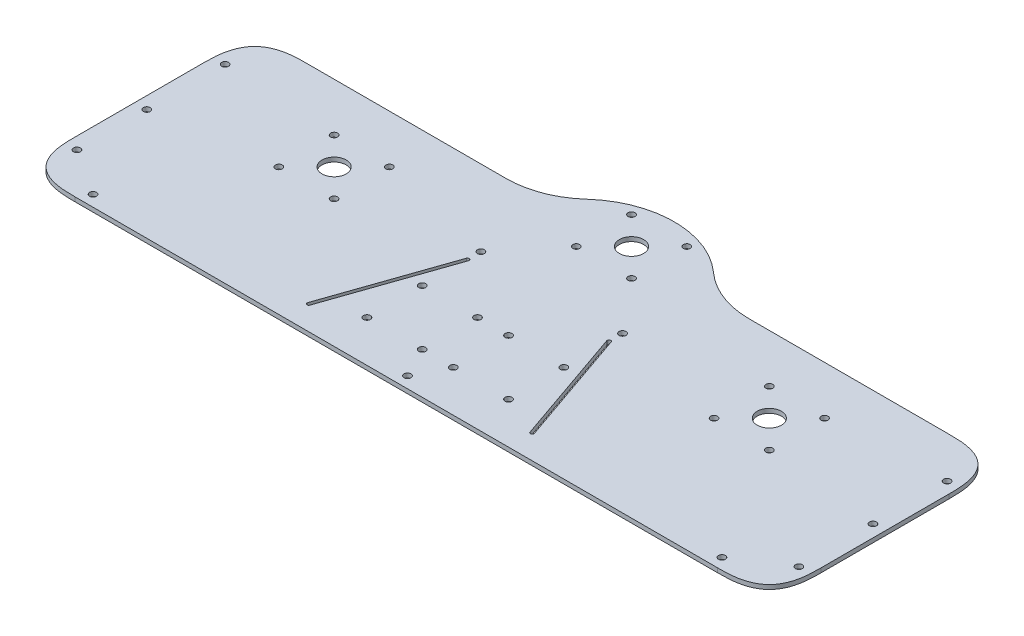
SolidWorks part; units mm, degrees
ref_plane "Front Plane" through (0, 0, 0) normal (0, 0, 1) x (1, 0, 0)
ref_plane "Top Plane" through (0, 0, 0) normal (0, 1, 0) x (1, 0, 0)
ref_plane "Right Plane" through (0, 0, 0) normal (1, 0, 0) x (0, 0, -1)
sketch "Sketch1" plane through (0, 0, 0) normal (0, 1, 0) x (1, 0, 0)
  line L1 (-103.134, 171.9149) -> (328.866, 171.9149)
  line L2 (-103.134, 171.9149) -> (-103.134, -28.0851)
  line L3 (-103.134, -28.0851) -> (328.866, -28.0851)
  line L4 (328.866, 171.9149) -> (328.866, -28.0851)
extrude "Boss-Extrude1" add sketch "Sketch1" along normal blind 2.5 contours L1 L4 L3 L2
sketch "Sketch3" plane through (0, 2.5, 0) normal (0, 1, 0) x (1, 0, 0)
  line L0 (-13.134, 71.9149) -> (-29.1359, 55.9131)
  line L1 (2.8678, 87.9167) -> (-29.1359, 87.9167)
  line L2 (2.8678, 87.9167) -> (2.8678, 55.9131)
  line L3 (2.8678, 55.9131) -> (-29.1359, 55.9131)
  line L4 (-29.1359, 87.9167) -> (-29.1359, 55.9131)
  line L5 (2.8678, 87.9167) -> (-29.1359, 55.9131) construction
  line L6 (2.8678, 55.9131) -> (-29.1359, 87.9167) construction
  line L7 (-103.134, 71.9149) -> (-13.134, 71.9149)
  line L8 (-103.134, 171.9149) -> (-103.134, -28.0851) construction
  line L9 (238.866, 71.9149) -> (238.866, 115.9149)
  line L14 (62.253, -0.3819) -> (46.2512, -16.3837)
  line L15 (238.866, 115.9149) -> (328.866, 115.9149)
  line L18 (328.866, 171.9149) -> (328.866, -28.0851) construction
  line L19 (238.866, 71.9149) -> (222.8641, 55.9131)
  line L20 (254.8678, 87.9167) -> (222.8641, 87.9167)
  line L21 (254.8678, 87.9167) -> (254.8678, 55.9131)
  line L22 (254.8678, 55.9131) -> (222.8641, 55.9131)
  line L23 (222.8641, 87.9167) -> (222.8641, 55.9131)
  line L24 (254.8678, 87.9167) -> (222.8641, 55.9131) construction
  line L25 (254.8678, 55.9131) -> (222.8641, 87.9167) construction
  line L27 (328.866, 71.9149) -> (238.866, 71.9149)
  line L28 (238.866, 115.9149) -> (238.866, 171.9149)
  line L29 (238.866, 171.9149) -> (328.866, 171.9149)
  line L30 (328.866, 115.9149) -> (328.866, 171.9149)
  line L31 (328.866, 115.9149) -> (-169.3435, 115.9149)
  line L32 (328.866, 115.9149) -> (328.866, 173.2785)
  line L33 (328.866, 173.2785) -> (-169.3435, 173.2785)
  line L34 (-169.3435, 115.9149) -> (-169.3435, 173.2785)
  line L35 (78.2549, 15.6199) -> (46.2512, 15.6199)
  line L36 (78.2549, 15.6199) -> (78.2549, -16.3837)
  line L37 (78.2549, -16.3837) -> (46.2512, -16.3837)
  line L38 (46.2512, 15.6199) -> (46.2512, -16.3837)
  line L39 (78.2549, 15.6199) -> (46.2512, -16.3837) construction
  line L40 (78.2549, -16.3837) -> (46.2512, 15.6199) construction
  circle A0 centre (-13.134, 71.9149) radius 7
  circle A1 centre (-29.1359, 55.9131) radius 2
  circle A2 centre (-29.1359, 87.9167) radius 2
  circle A3 centre (2.8678, 87.9167) radius 2
  circle A4 centre (2.8678, 55.9131) radius 2
  circle A10 centre (238.866, 71.9149) radius 7
  circle A11 centre (222.8641, 55.9131) radius 2
  circle A12 centre (222.8641, 87.9167) radius 2
  circle A13 centre (254.8678, 87.9167) radius 2
  circle A14 centre (254.8678, 55.9131) radius 2
  circle A15 centre (62.253, -0.3819) radius 7
  circle A16 centre (46.2512, -16.3837) radius 2
  circle A17 centre (46.2512, 15.6199) radius 2
  circle A18 centre (78.2549, 15.6199) radius 2
  circle A19 centre (78.2549, -16.3837) radius 2
  point P10 (328.866, 71.9149)
extrude "Cut-Extrude1" cut sketch "Sketch3" against normal blind 2.5 contours A2 | A3 | A4 | A1 | A0 | A11 | A14 | A13 | A10 | A12 | L32 L31 L34 L33
sketch "Sketch5" plane through (0, 2.5, 0) normal (0, 1, 0) x (1, 0, 0)
  line L0 (263.7413, -28.0851) -> (263.7413, -18.0851)
  line L3 (-103.134, -28.0851) -> (328.866, -28.0851) construction
  line L5 (263.7413, -18.0851) -> (328.866, -18.0851)
  line L6 (263.7413, -18.0851) -> (263.7413, -28.0851)
  line L7 (263.7413, -28.0851) -> (328.866, -28.0851)
  line L8 (328.866, -18.0851) -> (328.866, -28.0851)
  line L9 (263.7413, -18.0851) -> (-103.134, -18.0851)
  line L10 (263.7413, -18.0851) -> (263.7413, -28.0851)
  line L11 (263.7413, -28.0851) -> (-103.134, -28.0851)
  line L12 (-103.134, -18.0851) -> (-103.134, -28.0851)
  line M12 (328.866, -28.0851) -> (328.866, 115.9149)
  line M14 (-103.134, 115.9149) -> (-103.134, -28.0851)
  line M15 (-103.134, -28.0851) -> (328.866, -28.0851)
extrude "Cut-Extrude3" cut sketch "Sketch5" against normal blind 2.5 contours L0 L9 M14 M15 | L5 L0 M15 M12 region at (80.3036, 2.5, 23.0851) region at (296.3036, 2.5, 23.0851)
sketch "Sketch6" plane through (0, 2.5, 0) normal (0, 1, 0) x (1, 0, 0)
  line L0 (328.866, -18.0851) -> (-103.134, -18.0851) construction
  line L1 (112.866, -18.0851) -> (112.866, 21.9149)
  line L2 (112.866, 21.9149) -> (137.866, 21.9149)
  line L3 (112.866, 21.9149) -> (87.866, 21.9149)
  line L4 (87.866, 21.9149) -> (71.8641, 5.9131)
  line L5 (103.8678, 37.9167) -> (71.8641, 37.9167)
  line L6 (103.8678, 37.9167) -> (103.8678, 5.9131)
  line L7 (103.8678, 5.9131) -> (71.8641, 5.9131)
  line L8 (71.8641, 37.9167) -> (71.8641, 5.9131)
  line L9 (103.8678, 37.9167) -> (71.8641, 5.9131) construction
  line L10 (103.8678, 5.9131) -> (71.8641, 37.9167) construction
  line L11 (137.866, 21.9149) -> (121.8641, 5.9131)
  line L12 (153.8678, 37.9167) -> (121.8641, 37.9167)
  line L13 (153.8678, 37.9167) -> (153.8678, 5.9131)
  line L14 (153.8678, 5.9131) -> (121.8641, 5.9131)
  line L15 (121.8641, 37.9167) -> (121.8641, 5.9131)
  line L16 (153.8678, 37.9167) -> (121.8641, 5.9131) construction
  line L17 (153.8678, 5.9131) -> (121.8641, 37.9167) construction
  circle A0 centre (137.866, 21.9149) radius 16
  circle A1 centre (87.866, 21.9149) radius 16
  circle A2 centre (87.866, 21.9149) radius 7
  circle A3 centre (71.8641, 5.9131) radius 2
  circle A4 centre (71.8641, 37.9167) radius 2
  circle A5 centre (103.8678, 37.9167) radius 2
  circle A6 centre (103.8678, 5.9131) radius 2
  circle A7 centre (137.866, 21.9149) radius 7
  circle A8 centre (121.8641, 5.9131) radius 2
  circle A9 centre (121.8641, 37.9167) radius 2
  circle A10 centre (153.8678, 37.9167) radius 2
  circle A11 centre (153.8678, 5.9131) radius 2
  point P0 (112.866, -18.0851)
extrude "Cut-Extrude4" cut sketch "Sketch6" against normal blind 2.5 contours A11 | A8 | A10 | A9 | A5 | A6 | A3 | A4
sketch "Sketch8" plane through (0, 2.5, 0) normal (0, 1, 0) x (1, 0, 0)
  line L2 (153.8678, 5.9131) -> (153.8678, 90.0973)
  line L3 (153.8678, 90.0973) -> (71.8641, 90.0973)
  line L4 (71.8641, 90.0973) -> (71.8641, 5.9131)
  line L5 (153.8678, 64.0929) -> (71.8641, 64.0929)
  line L10 (177.527, -4.0851) -> (153.8678, 64.0929) construction
  line L14 (176.5823, -4.4129) -> (152.9231, 63.7651)
  line L15 (178.4718, -3.7572) -> (154.8125, 64.4208)
  line L16 (48.2049, -4.0851) -> (71.8641, 64.0929) construction
  line L17 (47.2602, -3.7572) -> (70.9194, 64.4208)
  line L18 (49.1496, -4.4129) -> (72.8089, 63.7651)
  arc A6 (176.5823, -4.4129) -> (178.4718, -3.7572) centre (177.527, -4.0851) ccw
  arc A7 (154.8125, 64.4208) -> (152.9231, 63.7651) centre (153.8678, 64.0929) ccw
  arc A8 (47.2602, -3.7572) -> (49.1496, -4.4129) centre (48.2049, -4.0851) ccw
  arc A9 (72.8089, 63.7651) -> (70.9194, 64.4208) centre (71.8641, 64.0929) ccw
  point P17 (177.527, 5.9131)
  point P18 (48.2049, 5.9131)
  point P19 (165.6974, 30.0039)
  point P22 (112.866, -4.0851)
  point P27 (60.0345, 30.0039)
extrude "Cut-Extrude5" cut sketch "Sketch8" against normal blind 2.5 contours L17 A9 L18 A8 | L15 A7 L14 A6
fillet "Fillet1" radius 30 4 edges at (-103.134, 1.25, -115.9149) (-103.134, 1.25, 18.0851) (328.866, 1.25, -115.9149) (328.866, 1.25, 18.0851) curvature continuous yes
sketch "Sketch9" plane through (0, 2.5, 0) normal (0, 1, 0) x (1, 0, 0)
  line L0 (328.866, 62.6221) -> (321.866, 62.6221)
  line L1 (328.866, 85.9149) -> (328.866, 11.9149) construction
  line L2 (321.866, 109.7214) -> (321.866, -11.8915)
  line L3 (321.866, 6.0103) -> (321.866, -11.8915)
  line L4 (321.866, 109.7214) -> (321.866, 91.8196)
  line L5 (321.866, 91.8196) -> (321.866, 109.7214)
  line L6 (-103.134, 46.4673) -> (-96.134, 46.4673)
  line L7 (-103.134, 85.9149) -> (-103.134, 11.9149) construction
  line L8 (-96.134, 46.4673) -> (-96.134, 109.7214)
  line L9 (-96.134, 109.7214) -> (-96.134, -11.8916)
  line L10 (-96.134, -11.8916) -> (-96.134, 6.0103)
  line L11 (-96.134, 109.7214) -> (-96.134, 97.3154)
  line L12 (-96.134, 109.7214) -> (-96.134, 91.8196)
  circle A0 centre (321.866, 6.0103) radius 2
  circle A1 centre (321.866, 48.9149) radius 2
  circle A2 centre (321.866, 91.8196) radius 2
  circle A3 centre (-96.134, 46.4673) radius 2
  circle A4 centre (-96.134, 91.8196) radius 2
  circle A5 centre (-96.134, 6.0103) radius 2
  spline S0 degree 2 poles (328.866, 85.9149) (328.866, 87.9765) (328.8467, 89.0459) (328.8162, 90.7467) (328.7231, 92.1742) (328.5043, 95.5283) (327.8783, 98.3317) (326.3274, 105.2776) (322.2688, 109.3319) (318.2198, 113.3765) (311.2895, 114.9258) (308.4764, 115.5546) (305.1048, 115.7733) (303.6844, 115.8655) (301.9893, 115.8958) (300.9233, 115.9149) (298.866, 115.9149) knots 0 0 0 0.0625 0.0625 0.125 0.125 0.25 0.25 0.5 0.5 0.75 0.75 0.875 0.875 0.9375 0.9375 1 1 1 construction
  spline S1 degree 2 poles (298.866, -18.0851) (300.9275, -18.0851) (301.997, -18.0659) (303.6978, -18.0353) (305.1253, -17.9422) (308.4794, -17.7234) (311.2827, -17.0975) (318.2287, -15.5466) (322.283, -11.4879) (326.3276, -7.4389) (327.8768, -0.5086) (328.5057, 2.3045) (328.7244, 5.6761) (328.8165, 7.0965) (328.8469, 8.7916) (328.866, 9.8575) (328.866, 11.9149) knots 0 0 0 0.0625 0.0625 0.125 0.125 0.25 0.25 0.5 0.5 0.75 0.75 0.875 0.875 0.9375 0.9375 1 1 1 construction
  spline S2 degree 2 poles (-73.134, 115.9149) (-75.1956, 115.9149) (-76.2651, 115.8957) (-77.9658, 115.8651) (-79.3933, 115.772) (-82.7474, 115.5532) (-85.5508, 114.9273) (-92.4967, 113.3764) (-96.551, 109.3177) (-100.5957, 105.2687) (-102.1449, 98.3384) (-102.7737, 95.5254) (-102.9924, 92.1538) (-103.0846, 90.7333) (-103.1149, 89.0383) (-103.134, 87.9723) (-103.134, 85.9149) knots 0 0 0 0.0625 0.0625 0.125 0.125 0.25 0.25 0.5 0.5 0.75 0.75 0.875 0.875 0.9375 0.9375 1 1 1 construction
  spline S3 degree 2 poles (-103.134, 11.9149) (-103.134, 9.8534) (-103.1148, 8.7839) (-103.0842, 7.0831) (-102.9911, 5.6556) (-102.7723, 2.3015) (-102.1464, -0.5019) (-100.5955, -7.4478) (-96.5368, -11.5021) (-92.4879, -15.5467) (-85.5575, -17.0959) (-82.7445, -17.7248) (-79.3729, -17.9435) (-77.9525, -18.0356) (-76.2574, -18.066) (-75.1914, -18.0851) (-73.134, -18.0851) knots 0 0 0 0.0625 0.0625 0.125 0.125 0.25 0.25 0.5 0.5 0.75 0.75 0.875 0.875 0.9375 0.9375 1 1 1 construction
extrude "Cut-Extrude6" cut sketch "Sketch9" against normal blind 2.5 contours A0 | A1 | A2 | A5 | A3 | A4
sketch "Sketch10" plane through (0, 2.5, 0) normal (0, 1, 0) x (1, 0, 0)
  line L0 (232.1904, -18.0851) -> (232.1904, -11.5851)
  line L1 (298.866, -18.0851) -> (-73.134, -18.0851) construction
  line L2 (322.1851, -11.5851) -> (-96.4532, -11.5851)
  line L3 (322.1851, -11.5851) -> (232.1904, -11.5851)
  line L4 (322.1851, -11.5851) -> (232.1904, -11.5851)
  line L5 (322.1851, -11.5851) -> (232.1904, -11.5851)
  line L6 (322.1851, -11.5851) -> (294.9418, -11.5851)
  line L7 (-96.4532, -11.5851) -> (-78.7572, -11.5851)
  line L8 (-96.4532, -11.5851) -> (-69.2097, -11.5851)
  circle A0 centre (112.866, -11.5851) radius 2
  circle A3 centre (294.9418, -11.5851) radius 2
  circle A4 centre (-69.2097, -11.5851) radius 2
  spline S0 degree 2 poles (298.866, -18.0851) (300.9275, -18.0851) (301.997, -18.0659) (303.6978, -18.0353) (305.1253, -17.9422) (308.4794, -17.7234) (311.2827, -17.0975) (318.2287, -15.5466) (322.283, -11.4879) (326.3276, -7.4389) (327.8768, -0.5086) (328.5057, 2.3045) (328.7244, 5.6761) (328.8165, 7.0965) (328.8469, 8.7916) (328.866, 9.8575) (328.866, 11.9149) knots 0 0 0 0.0625 0.0625 0.125 0.125 0.25 0.25 0.5 0.5 0.75 0.75 0.875 0.875 0.9375 0.9375 1 1 1 construction
  spline S1 degree 2 poles (-103.134, 11.9149) (-103.134, 9.8534) (-103.1148, 8.7839) (-103.0842, 7.0831) (-102.9911, 5.6556) (-102.7723, 2.3015) (-102.1464, -0.5019) (-100.5955, -7.4478) (-96.5368, -11.5021) (-92.4879, -15.5467) (-85.5575, -17.0959) (-82.7445, -17.7248) (-79.3729, -17.9435) (-77.9525, -18.0356) (-76.2574, -18.066) (-75.1914, -18.0851) (-73.134, -18.0851) knots 0 0 0 0.0625 0.0625 0.125 0.125 0.25 0.25 0.5 0.5 0.75 0.75 0.875 0.875 0.9375 0.9375 1 1 1 construction
extrude "Cut-Extrude7" cut sketch "Sketch10" against normal blind 2.5 contours A4 | A0 | A3
sketch "Sketch11" plane through (0, 2.5, 0) normal (0, 1, 0) x (1, 0, 0)
  line L0 (71.8641, 37.9167) -> (71.8641, 115.9149)
  line L1 (298.866, 115.9149) -> (-73.134, 115.9149) construction
  line L2 (153.8678, 37.9167) -> (153.8678, 115.9149)
  line L3 (-13.134, 71.9149) -> (170.9876, 71.9149)
  line L4 (121.8641, 37.9167) -> (121.8641, 95.7488)
  line L5 (121.8641, 71.9149) -> (105.8623, 55.9131)
  line L6 (137.866, 87.9167) -> (105.8623, 87.9167)
  line L7 (137.866, 87.9167) -> (137.866, 55.9131)
  line L8 (137.866, 55.9131) -> (105.8623, 55.9131)
  line L9 (105.8623, 87.9167) -> (105.8623, 55.9131)
  line L10 (137.866, 87.9167) -> (105.8623, 55.9131) construction
  line L11 (137.866, 55.9131) -> (105.8623, 87.9167) construction
  circle A1 centre (121.8641, 71.9149) radius 7
  circle A3 centre (105.8623, 55.9131) radius 2
  circle A4 centre (105.8623, 87.9167) radius 2
  circle A5 centre (137.866, 87.9167) radius 2
  circle A6 centre (137.866, 55.9131) radius 2
  circle A7 centre (153.8678, 71.9149) radius 2
  circle A9 centre (71.8641, 71.9149) radius 2
extrude "Cut-Extrude8" cut sketch "Sketch11" against normal blind 10 contours A7 | A9
sketch "Sketch12" plane through (0, 2.5, 0) normal (0, 1, 0) x (1, 0, 0)
  line L0 (112.866, -9.5851) -> (112.866, 115.9149)
  line L1 (298.866, 115.9149) -> (-73.134, 115.9149) construction
  line L2 (112.866, 115.9149) -> (112.866, 118.1149)
  line L3 (112.866, 118.1149) -> (96.8641, 102.1131)
  line L4 (128.8678, 134.1167) -> (96.8641, 134.1167)
  line L5 (128.8678, 134.1167) -> (128.8678, 102.1131)
  line L6 (128.8678, 102.1131) -> (96.8641, 102.1131)
  line L7 (96.8641, 134.1167) -> (96.8641, 102.1131)
  line L8 (128.8678, 134.1167) -> (96.8641, 102.1131) construction
  line L9 (128.8678, 102.1131) -> (96.8641, 134.1167) construction
  circle A0 centre (112.866, -11.5851) radius 2 construction
  circle A1 centre (112.866, 118.1149) radius 3
  circle A3 centre (112.866, 118.1149) radius 18.75
  circle A4 centre (112.866, 118.1149) radius 7
  circle A5 centre (96.8641, 102.1131) radius 2
  circle A6 centre (96.8641, 134.1167) radius 2
  circle A7 centre (128.8678, 134.1167) radius 2
  circle A8 centre (128.8678, 102.1131) radius 2
  arc A9 (65.5257, 115.9149) -> (160.2063, 115.9149) centre (112.866, 87.9167) cw
  line M34 (298.866, 115.9149) -> (-73.134, 115.9149)
extrude "Boss-Extrude2" add sketch "Sketch12" against normal blind 2.5 contours A4 L5 A3 L4 L7 M34 | L4 A3 | A3 L5 M34 | L7 A3 M34 | A6 L7 A3 L4 | A7 L4 A3 L5 | A9 A3 L7 A6 L4 A7 L5 M34 region at (112.866, 2.5, -125.7158) region at (130.035, 2.5, -120.6361) region at (132.5664, 2.5, -116.9551) region at (95.6969, 2.5, -120.6361) region at (126.7073, 2.5, -131.9563) region at (99.0246, 2.5, -131.9563) region at (112.866, 2.5, -135.2232)
sketch "Sketch13" plane through (0, 2.5, 0) normal (0, 1, 0) x (1, 0, 0)
  line L0 (112.866, 118.1149) -> (96.8641, 102.1131)
  line L1 (128.8678, 134.1167) -> (96.8641, 134.1167)
  line L2 (128.8678, 134.1167) -> (128.8678, 102.1131)
  line L3 (128.8678, 102.1131) -> (96.8641, 102.1131)
  line L4 (96.8641, 134.1167) -> (96.8641, 102.1131)
  line L5 (128.8678, 134.1167) -> (96.8641, 102.1131) construction
  line L6 (128.8678, 102.1131) -> (96.8641, 134.1167) construction
  circle A0 centre (112.866, 118.1149) radius 18.75
  circle A1 centre (112.866, 118.1149) radius 7
  circle A2 centre (96.8641, 102.1131) radius 2
  circle A3 centre (96.8641, 134.1167) radius 2
  circle A4 centre (128.8678, 134.1167) radius 2
  circle A5 centre (128.8678, 102.1131) radius 2
  point P0 (112.866, 118.1149)
extrude "Cut-Extrude9" cut sketch "Sketch13" against normal blind 2.5 contours A5 | A1 | A2 | A3 | A4
fillet "Fillet2" radius 50 2 edges at (65.5257, 1.25, -115.9149) (160.2063, 1.25, -115.9149)
